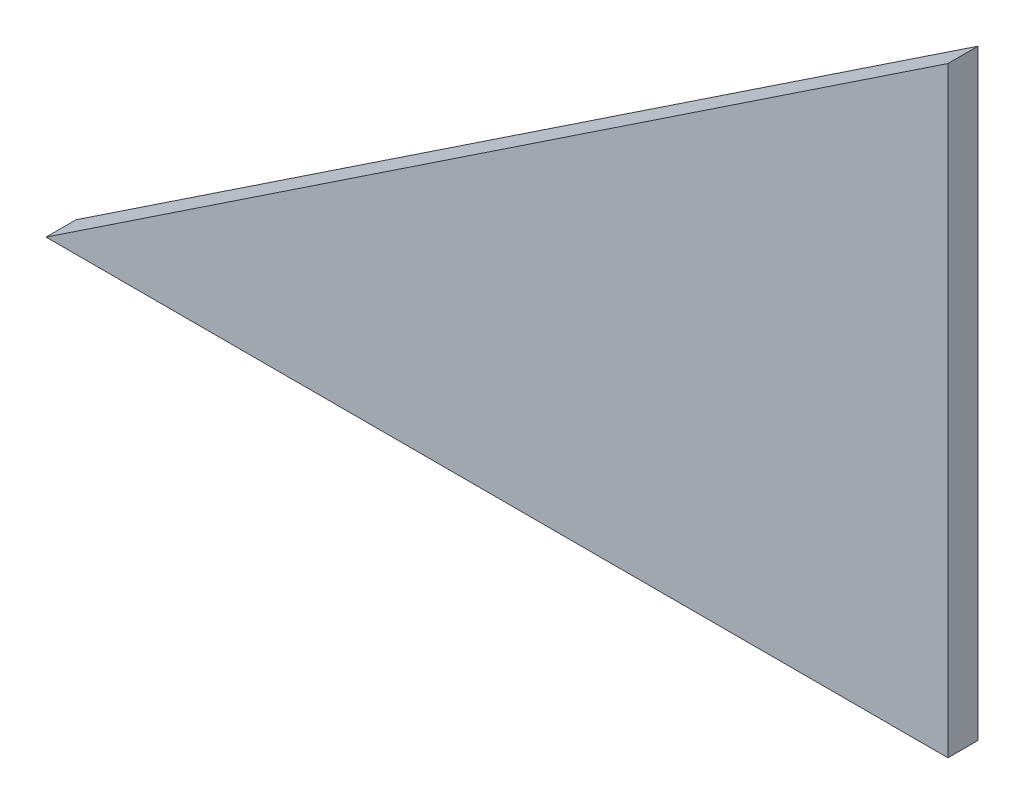
SolidWorks part; units mm, degrees
ref_plane "Front Plane" through (0, 0, 0) normal (0, 0, 1) x (1, 0, 0)
ref_plane "Top Plane" through (0, 0, 0) normal (0, 1, 0) x (1, 0, 0)
ref_plane "Right Plane" through (0, 0, 0) normal (1, 0, 0) x (0, 0, -1)
sketch "Sketch1" plane through (0, 0, 25.264) normal (0, 0, -1) x (-1, 0, 0)
  line L0 (-209.0016, 11.9601) -> (-209.0016, 37.3601)
  line L1 (-209.5096, 11.9601) -> (-6.3096, 11.9601) construction
  line L2 (-209.0016, 13.2301) -> (-209.0016, 54.5051) construction
  line L3 (-209.0016, 37.3601) -> (-170.9016, 11.9601)
  line L4 (-170.9016, 11.9601) -> (-209.0016, 11.9601)
  dimension "D1" = 25.4
  dimension "D2" = 38.1
extrude "Boss-Extrude1" add sketch "Sketch1" along normal blind 1.27
